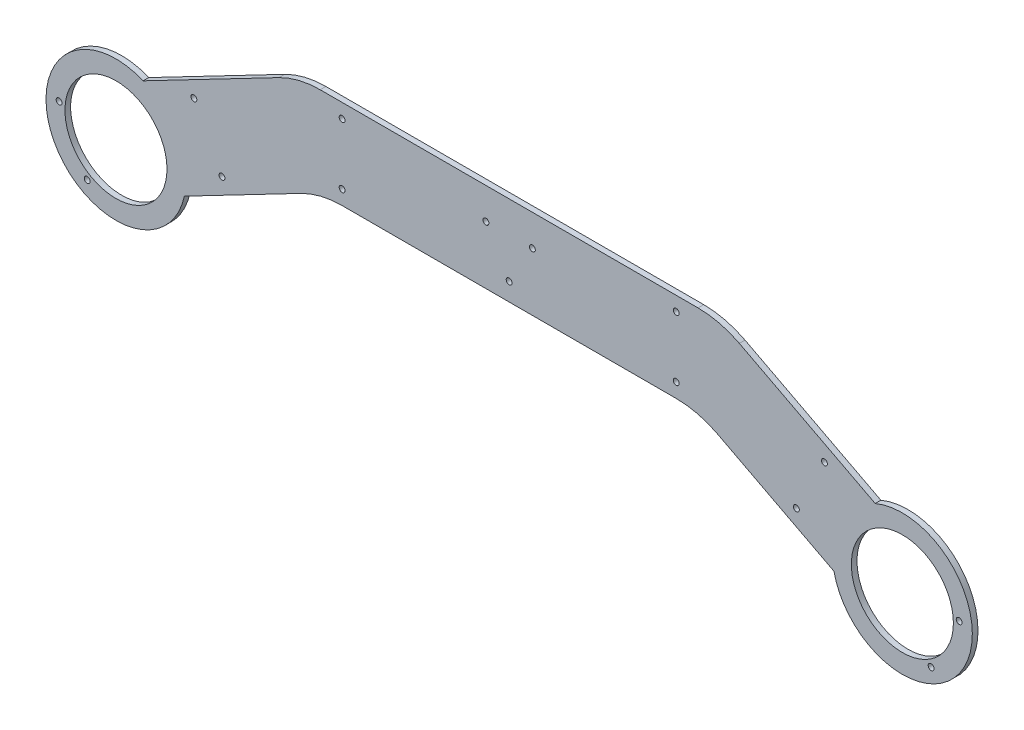
SolidWorks part; units mm, degrees
material "6061-T6 (SS)"
ref_plane "Front Plane" through (0, 0, 0) normal (0, 0, 1) x (1, 0, 0)
ref_plane "Top Plane" through (0, 0, 0) normal (0, 1, 0) x (1, 0, 0)
ref_plane "Right Plane" through (0, 0, 0) normal (1, 0, 0) x (0, 0, -1)
sketch "Sketch1" plane through (0, 0, 0) normal (0, 0, 1) x (1, 0, 0)
  line L0 (0, -33.2132) -> (0, -83.2132) construction
  line L1 (105.7091, -33.2132) -> (-105.7091, -33.2132)
  line L2 (-128.7965, -38.8627) -> (-262.5891, -108.5107)
  line L3 (-262.5891, -108.5107) -> (-239.5017, -152.8612)
  line L4 (-239.5017, -152.8612) -> (-116.5616, -88.8627)
  line L5 (-93.4741, -83.2132) -> (93.4741, -83.2132)
  line L6 (116.5616, -88.8627) -> (239.5017, -152.8612)
  line L7 (239.5017, -152.8612) -> (262.5891, -108.5107)
  line L8 (262.5891, -108.5107) -> (128.7965, -38.8627)
  line L9 (-117.944, -33.2132) -> (0, 28.1845) construction
  line L10 (0, 28.1845) -> (117.944, -33.2132) construction
  line L11 (-251.0454, -130.686) -> (-220, -114.5248) construction
  line L12 (251.0454, -130.686) -> (220, -114.5248) construction
  line L13 (-330, -114.5248) -> (-110, -114.5248) construction
  line L14 (-110, -114.5248) -> (110, -114.5248) construction
  line L15 (0, 0) -> (17.6777, -17.6777) construction
  line L16 (28.2843, -7.0711) -> (7.0711, -28.2843) construction
  line L17 (-7.0711, -28.2843) -> (-17.6777, -17.6777) construction
  line L18 (-17.6777, -17.6777) -> (17.6777, 17.6777) construction
  line L19 (17.6777, 17.6777) -> (28.2843, 7.0711) construction
  line L20 (17.6777, 17.6777) -> (67.5526, 17.6777) construction
  line L21 (0, -35.3553) -> (35.3553, 0) construction
  line L22 (0, 0) -> (6.9629, -24.0108) construction
  line L23 (-7.4435, -28.1885) -> (21.3694, -19.833) construction
  circle A1 centre (0, 0) radius 7.9375 construction
  circle A2 centre (-220, -114.5248) radius 110 construction
  circle A3 centre (220, -114.5248) radius 110 construction
  arc A4 (28.2843, -7.0711) -> (28.2843, 7.0711) centre (21.2132, 0) ccw construction
  arc A5 (7.0711, -28.2843) -> (-7.0711, -28.2843) centre (0, -21.2132) cw construction
  arc A6 (93.4741, -83.2132) -> (116.5616, -88.8627) centre (93.4741, -133.2132) cw
  arc A7 (-116.5616, -88.8627) -> (-93.4741, -83.2132) centre (-93.4741, -133.2132) cw
  arc A8 (128.7965, -38.8627) -> (105.7091, -33.2132) centre (105.7091, -83.2132) ccw
  arc A9 (-105.7091, -33.2132) -> (-128.7965, -38.8627) centre (-105.7091, -83.2132) ccw
  circle A10 centre (0, 0) radius 7.9375 construction
  arc A11 (21.3694, -19.833) -> (28.1885, -7.4435) centre (18.5842, -10.2287) ccw construction
  point P26 (17.6777, -17.6777)
  point P33 (35.3553, 0)
  point P36 (0, -35.3553)
  point P40 (0, -31.2132)
  dimension "D12" = 50
  dimension "D2" = 220
  dimension "D1" = 50
  dimension "D3" = 125
  dimension "D5" = 35
  dimension "D8" = 45
  dimension "D10" = 2
extrude "Base" add sketch "Sketch1" along normal blind 3.175
fillet "Fillet1" radius 10 4 edges at (262.5891, -108.5107, 1.5875) (239.5017, -152.8612, 1.5875) (-239.5017, -152.8612, 1.5875) (-262.5891, -108.5107, 1.5875)
sketch "Sketch2" plane through (0, 0, 3.175) normal (0, 0, 1) x (1, 0, 0)
  line L0 (0, -33.2132) -> (0, -83.2132) construction
  line L1 (105.7091, -33.2132) -> (-105.7091, -33.2132) construction
  line L2 (-93.4741, -83.2132) -> (93.4741, -83.2132) construction
  circle A0 centre (0, -58.2132) radius 15 construction
  circle A1 centre (-12.9904, -50.7132) radius 1.65
  circle A2 centre (12.9904, -50.7132) radius 1.65
  circle A3 centre (0, -73.2132) radius 1.65
  point P17 (0, -58.2132)
  dimension "D1" = 30
  dimension "D2" = 3.3
  dimension "D3" = 3
extrude "Adapter Attachment" cut sketch "Sketch2" against normal through all
sketch "Sketch3" plane through (0, 0, 3.175) normal (0, 0, 1) x (1, 0, 0)
  line L0 (-258.6387, -109.7562) -> (-249.1015, -112.7633) construction
  line L1 (-238.2561, -148.9108) -> (-235.249, -139.3736) construction
  line L2 (-251.799, -111.9128) -> (-255.493, -104.8167) construction
  line L3 (-236.0996, -142.0711) -> (-232.4056, -149.1672) construction
  line L4 (-128.7965, -38.8627) -> (-253.719, -103.8932) construction
  line L5 (-230.6316, -148.2437) -> (-116.5616, -88.8627) construction
  line L6 (0, -1.7463) -> (0, 1.7463) construction
  line L7 (-236.0996, -142.0711) -> (-160.7036, -102.8225) construction
  line L8 (-176.4031, -72.6641) -> (-251.799, -111.9128) construction
  line L9 (-93.4741, -83.2132) -> (-93.4741, -75.2132) construction
  line L10 (-93.4741, -83.2132) -> (93.4741, -83.2132) construction
  line L11 (-93.4741, -41.2132) -> (-93.4741, -33.2132) construction
  line L12 (105.7091, -33.2132) -> (-105.7091, -33.2132) construction
  arc A0 (-253.719, -103.8932) -> (-257.9716, -117.3808) centre (-249.1015, -112.7633) ccw construction
  arc A1 (-244.1191, -143.9911) -> (-230.6316, -148.2437) centre (-235.249, -139.3736) ccw construction
  circle A2 centre (-251.799, -111.9128) radius 1.65
  circle A3 centre (-236.0996, -142.0711) radius 1.65
  circle A4 centre (-160.7036, -102.8225) radius 1.65
  circle A5 centre (-176.4031, -72.6641) radius 1.65
  circle A6 centre (-93.4741, -75.2132) radius 1.65
  circle A7 centre (-93.4741, -41.2132) radius 1.65
  circle A8 centre (93.4741, -41.2132) radius 1.65
  circle A9 centre (93.4741, -75.2132) radius 1.65
  circle A10 centre (176.4031, -72.6641) radius 1.65
  circle A11 centre (160.7036, -102.8225) radius 1.65
  circle A12 centre (251.799, -111.9128) radius 1.65
  circle A13 centre (236.0996, -142.0711) radius 1.65
  dimension "D2" = 3.3
  dimension "D1" = 8
  dimension "D4" = 85
extrude "Strut Holes" cut sketch "Sketch3" against normal through all
sketch "Sketch4" plane through (0, 0, 3.175) normal (0, 0, 1) x (1, 0, 0)
  line L0 (-241.4586, -107.7589) -> (-213.2341, -93.0661) construction
  line L1 (-128.7965, -38.8627) -> (-262.5891, -108.5107) construction
  line L2 (0, -1.7463) -> (0, 1.7463) construction
  circle A0 centre (-220, -114.5248) radius 16.05
  circle A1 centre (-220, -114.5248) radius 22.5 construction
  circle A2 centre (-241.4586, -107.7589) radius 2.75
  circle A3 centre (-213.2341, -93.0661) radius 2.75
  circle A4 centre (-198.5414, -121.2906) radius 2.75
  circle A5 centre (-226.7659, -135.9834) radius 2.75
  circle A6 centre (226.7659, -135.9834) radius 2.75
  circle A7 centre (241.4586, -107.7589) radius 2.75
  circle A8 centre (198.5414, -121.2906) radius 2.75
  circle A9 centre (213.2341, -93.0661) radius 2.75
  circle A10 centre (220, -114.5248) radius 16.05
  point P15 (-220, -114.5248)
  dimension "D1" = 32.1
  dimension "D2" = 45
  dimension "D4" = 5.5
  dimension "D3" = 4
extrude "Motor Connection" [suppressed] cut sketch "Sketch4" against normal through all
sketch "Sketch5" plane through (0, 0, 3.175) normal (0, 0, 1) x (1, 0, 0)
  line L0 (0, -1.7463) -> (0, 1.7463) construction
  circle A0 centre (-220, -114.5248) radius 28.55
  circle A1 centre (-220, -114.5248) radius 39.1548
  arc A2 (-253.719, -103.8932) -> (-257.9716, -117.3808) centre (-249.1015, -112.7633) ccw construction
  circle A3 centre (-236.0996, -142.0711) radius 1.65 construction
  circle A4 centre (-251.799, -111.9128) radius 1.65 construction
  circle A5 centre (-236.0996, -142.0711) radius 1.65
  circle A6 centre (-251.799, -111.9128) radius 1.65
  circle A7 centre (251.799, -111.9128) radius 1.65
  circle A8 centre (236.0996, -142.0711) radius 1.65
  circle A9 centre (220, -114.5248) radius 39.1548
  circle A10 centre (220, -114.5248) radius 28.55
  line M20 (253.719, -103.8932) -> (128.7965, -38.8627)
  line M24 (-128.7965, -38.8627) -> (-253.719, -103.8932)
  line M28 (-230.6316, -148.2437) -> (-116.5616, -88.8627)
  line M32 (116.5616, -88.8627) -> (230.6316, -148.2437)
  dimension "D1" = 57.1
extrude "Motor Ring" add sketch "Sketch5" against normal up to surface (3.175 mm away) up to face at (-250.149, -111.9128, 0)
extrude "Motor Slot" cut sketch "Sketch5<2>" against normal through all contours A0 M24 M28 | A10 M32 M20 region at (-220, -114.5248, 3.175) region at (220, -114.5248, 3.175)
sketch "Sketch5<2>" plane through (0, 0, 3.175) normal (0, 0, 1) x (1, 0, 0) same geometry as "Sketch5"
equation "\"D2@Sketch1\"=\"Wheel Diameter@Rocker Bogie Assy.Assembly\""
equation "\"D1@Base\"=\"Plate Thickness@Rocker Bogie Assy.Assembly\""
equation "\"D3@Sketch1\"=\"Bogie Angle@Rocker Bogie Assy.Assembly\""
